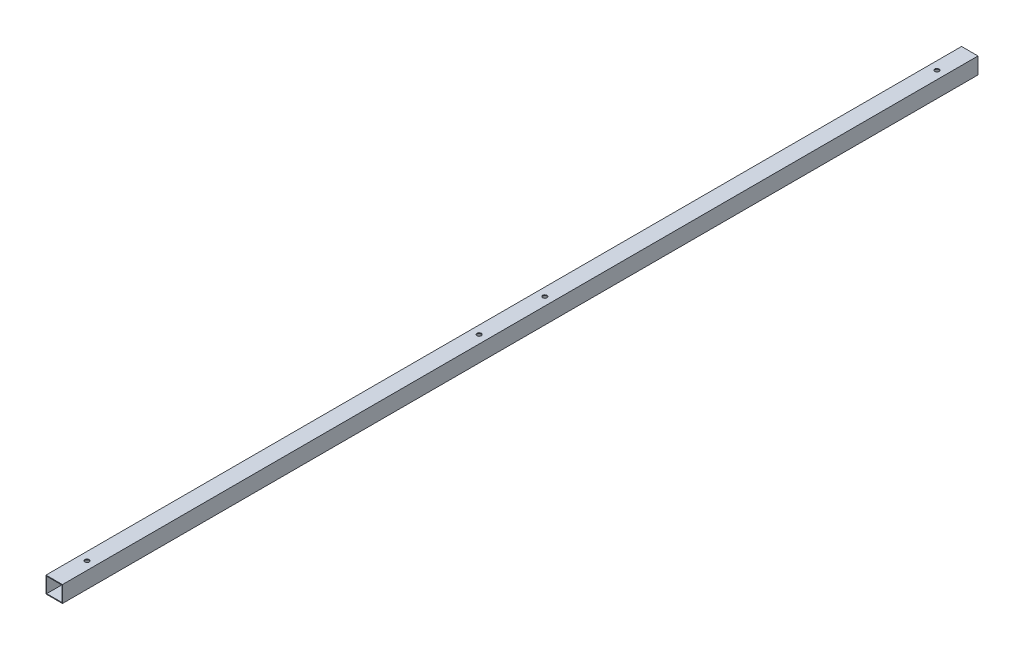
SolidWorks part; units mm, degrees
material "Plain Carbon Steel"
ref_plane "Front Plane" through (0, 0, 0) normal (0, 0, 1) x (1, 0, 0)
ref_plane "Top Plane" through (0, 0, 0) normal (0, 1, 0) x (1, 0, 0)
ref_plane "Right Plane" through (0, 0, 0) normal (1, 0, 0) x (0, 0, -1)
sketch "Sketch2" plane through (0, 0, 0) normal (0, 0, 1) x (1, 0, 0)
  line L0 (0, 19.05) -> (1.5875, 19.05) construction
  line L1 (0, 0) -> (38.1, 0)
  line L2 (0, 0) -> (0, 38.1)
  line L3 (0, 38.1) -> (38.1, 38.1)
  line L4 (38.1, 0) -> (38.1, 38.1)
  line L5 (1.5875, 1.5875) -> (36.5125, 1.5875)
  line L6 (1.5875, 1.5875) -> (1.5875, 36.5125)
  line L7 (1.5875, 36.5125) -> (36.5125, 36.5125)
  line L8 (36.5125, 1.5875) -> (36.5125, 36.5125)
  line L9 (19.05, 36.5125) -> (19.05, 38.1) construction
  line L10 (36.5125, 19.05) -> (38.1, 19.05) construction
  line L11 (19.05, 0) -> (19.05, 1.5875) construction
  dimension "D1" = 38.1
  dimension "D2" = 1.5875
  dimension "D3" = 38.1
extrude "Boss-Extrude1" add sketch "Sketch2" along normal blind 2120.9
hole_wizard "X (0.397) Diameter Hole1" positions "Sketch4" profile "Sketch3" hole size "X" standard "ANSI Inch" end condition through all
sketch "Sketch4" plane through (0, 0, 0) normal (0, -1, 0) x (-1, 0, 0)
  line L0 (-19.05, -2120.9) -> (-19.05, -2044.7) construction
  line L1 (0, -2120.9) -> (-38.1, -2120.9) construction
  line L2 (-19.05, -2044.7) -> (-19.05, -1136.65) construction
  line L3 (-19.05, -1136.65) -> (-19.05, -984.25) construction
  line L4 (-19.05, -984.25) -> (-19.05, -76.2) construction
  line L5 (-19.05, -76.2) -> (-19.05, 0) construction
  line L6 (0, 0) -> (-38.1, 0) construction
  point P0 (-19.05, -2044.7)
  point P2 (-19.05, -1136.65)
  point P4 (-19.05, -984.25)
  point P6 (-19.05, -76.2)
  dimension "D1" = 76.2
  dimension "D2" = 152.4
sketch "Sketch3" plane through (19.05, 0, 2044.7) normal (1, 0, 0) x (0, 0, -1)
  line L0 (0, 0) -> (0, 38.1)
  line L1 (0, 38.1) -> (5.0419, 38.1)
  line L2 (5.0419, 38.1) -> (5.0419, 0)
  line L5 (5.0419, 0) -> (0, 0)
  line L11 (0, -6.35) -> (0, 107.95) construction
  dimension "Thru Hole Dia." = 10.0838
  dimension "Thru Hole Depth" = 38.1
